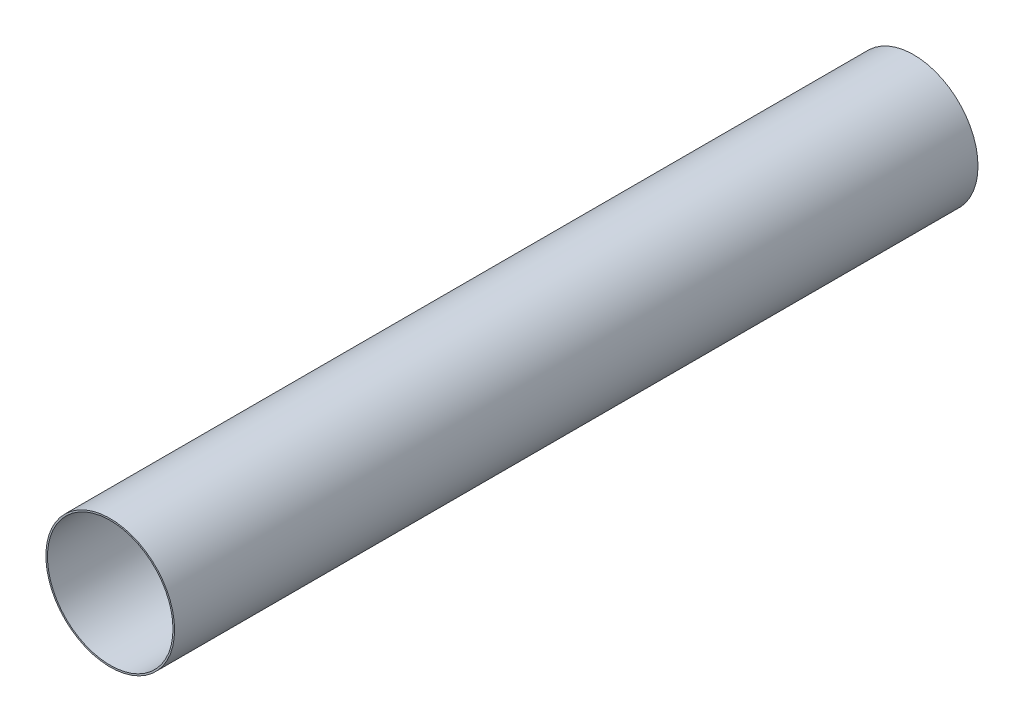
SolidWorks part; units mm, degrees
material "Thornel Mat VMA"
ref_plane "Front Plane" through (0, 0, 0) normal (0, 0, 1) x (1, 0, 0)
ref_plane "Top Plane" through (0, 0, 0) normal (0, 1, 0) x (1, 0, 0)
ref_plane "Right Plane" through (0, 0, 0) normal (1, 0, 0) x (0, 0, -1)
sketch "Sketch1" plane through (0, 0, 0) normal (0, 0, 1) x (1, 0, 0)
  circle A0 centre (0, 0) radius 81.375
  circle A1 centre (0, 0) radius 79.375
  dimension "D1" = 158.75
  dimension "D2" = 162.75
extrude "Boss-Extrude1" add sketch "Sketch1" along normal mid plane 1016
equation "\"TubeDiameter\" = 6.250in"
equation "\"D1@Sketch1\"=\"TubeDiameter\""
equation "\"D2@Sketch1\"=\"TubeDiameter\"+4mm"
